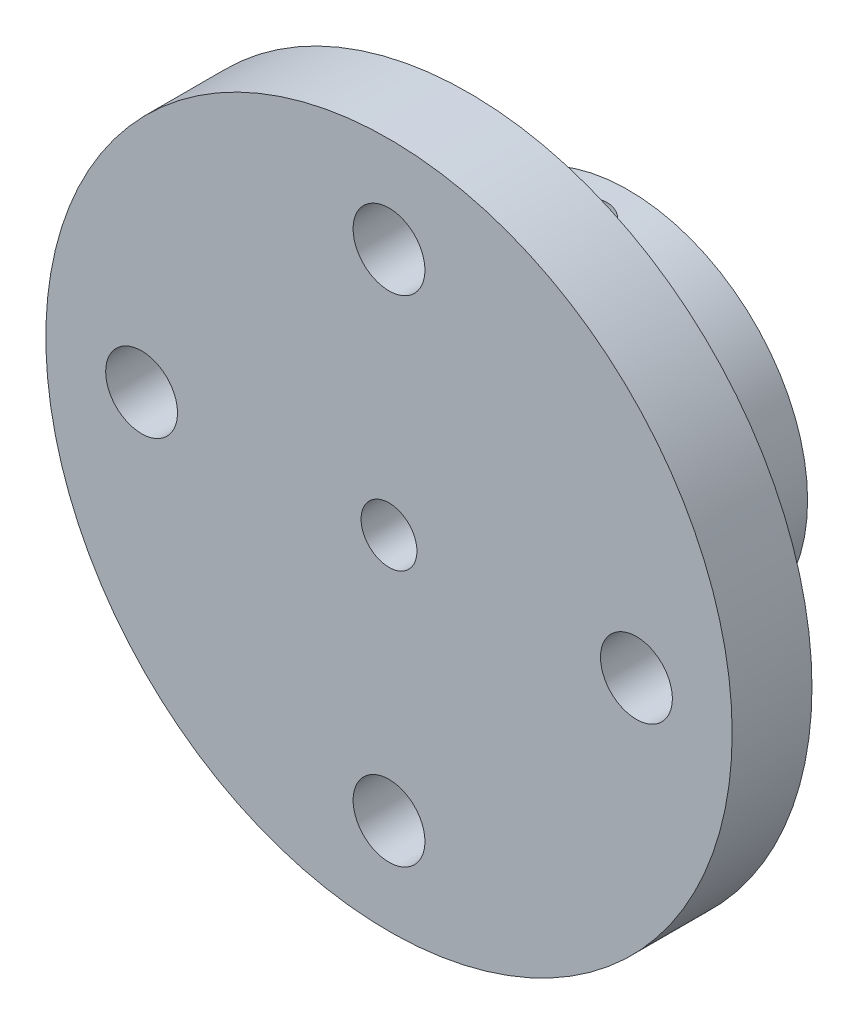
SolidWorks part; units mm, degrees
material "ABS"
ref_plane "Front Plane" through (0, 0, 0) normal (0, 0, 1) x (1, 0, 0)
ref_plane "Top Plane" through (0, 0, 0) normal (0, 1, 0) x (1, 0, 0)
ref_plane "Right Plane" through (0, 0, 0) normal (1, 0, 0) x (0, 0, -1)
sketch "Sketch1" plane through (0, 0, 0) normal (1, 0, 0) x (0, 0, -1)
  line L0 (-486.8485, 0) -> (23855.5787, 0) construction
  line L1 (0, 21.5) -> (5, 21.5)
  line L2 (5, 21.5) -> (9, 11.225)
  line L3 (9, 11.225) -> (15, 11.225)
  line L4 (15, 11.225) -> (15, 3.225)
  line L5 (15, 3.225) -> (0, 3.225)
  line L6 (0, 3.225) -> (0, 21.5)
  line L7 (0, 15.5) -> (7.3358, 15.5) construction
  dimension "D1" = 5
  dimension "D2" = 6.45
  dimension "D3" = 8
  dimension "D4" = 6
  dimension "D5" = 4
  dimension "D6" = 6
  dimension "D7" = 15.5
revolve "Revolve1" add sketch "Sketch1" angle 360 about L0
ref_plane "Plane1" through (0, 0, -9) normal (0, 0, 1) x (1, 0, 0)
sketch "Sketch11" plane through (0, 0, 0) normal (0, 0, 1) x (1, 0, 0)
  circle A0 centre (0, 0) radius 3.225
  circle A2 centre (0, 0) radius 3.225 construction
  circle A3 centre (0, 0) radius 1.75
  dimension "D1" = 3.5
extrude "Boss-Extrude2" add sketch "Sketch11" against normal blind 7
sketch "Sketch3" plane through (0, 0, -9) normal (0, 0, 1) x (1, 0, 0)
  point P0 (0, 15.5)
hole_wizard "CBORE for M4 SHCS1" positions "Sketch3" profile "Sketch4" counterbore size "M4" standard "ANSI Metric" end condition through all
sketch "Sketch4" plane through (0, 15.5, -9) normal (1, 0, 0) x (0, 1, 0)
  line L0 (0, 0) -> (0, 9)
  line L1 (0, 9) -> (2.25, 9)
  line L3 (2.25, 9) -> (2.25, 4)
  line L4 (2.25, 4) -> (4, 4)
  line L5 (4, 4) -> (4, 0)
  line L7 (4, 0) -> (0, 0)
  line L11 (0, -6.35) -> (0, 107.95) construction
  dimension "Thru Hole Dia." = 4.5
  dimension "Thru Hole Depth" = 9
  dimension "C'Bore Dia." = 8
  dimension "C'Bore Depth" = 4
pattern_circular "CirPattern1" count 4 over 360 about axis through (0, 0, 486.8485) along (0, 0, 1) of "CBORE for M4 SHCS1" reverse direction yes
sketch "Sketch6" plane through (0, 0, 0) normal (0, 0, 1) x (1, 0, 0)
  line L0 (-1.5375, 2.8349) -> (1.5375, 2.8349)
  circle A0 centre (0, 0) radius 3.225 construction
  circle A1 centre (0, 0) radius 3.225
  dimension "D1" = 3.075
extrude "Boss-Extrude1" add sketch "Sketch6" against normal up to surface (15 mm away) contours L0 A1 region at (0, 2.9918, 0) up to face at (11.225, 0, -15)
sketch "Sketch8" plane through (0, 2.8349, 0) normal (0, -1, 0) x (1, 0, 0)
  line L0 (0, -15) -> (0, -12)
  line L1 (-11.225, -15) -> (11.225, -15) construction
  dimension "D1" = 3
sketch "Sketch9" plane through (0, 0, 0) normal (0, -1, 0) x (-1, 0, 0)
  point P0 (0, 12)
hole_wizard "M4x0.7 Tapped Hole1" positions "Sketch9" profile "Sketch10" tap size "M4x0.7" standard "ANSI Metric" end condition through all
cosmetic thread "Hole Thread3" parameters "D2"=4
sketch "Sketch10" plane through (0, 0, -12) normal (1, 0, 0) x (0, 0, -1)
  line L0 (0, 0) -> (0, 21.5)
  line L1 (0, 21.5) -> (1.65, 21.5)
  line L2 (1.65, 21.5) -> (1.65, 0)
  line L5 (1.65, 0) -> (0, 0)
  line L11 (0, -6.35) -> (0, 107.95) construction
  dimension "Thru Tap Drill Dia." = 3.3
  dimension "Thru Tap Drill Depth" = 21.5
pattern_circular "CirPattern2" count 2 every 120 about axis through (0, 0, 486.8485) along (0, 0, 1) of "M4x0.7 Tapped Hole1"
cosmetic thread "Hole Thread4" parameters "D2"=4
chamfer "Chamfer1" distance 2 angle 45 1 edges at (11.225, 0, -9) first distance on face at (-8.8154, -6.949, -12.3596)
